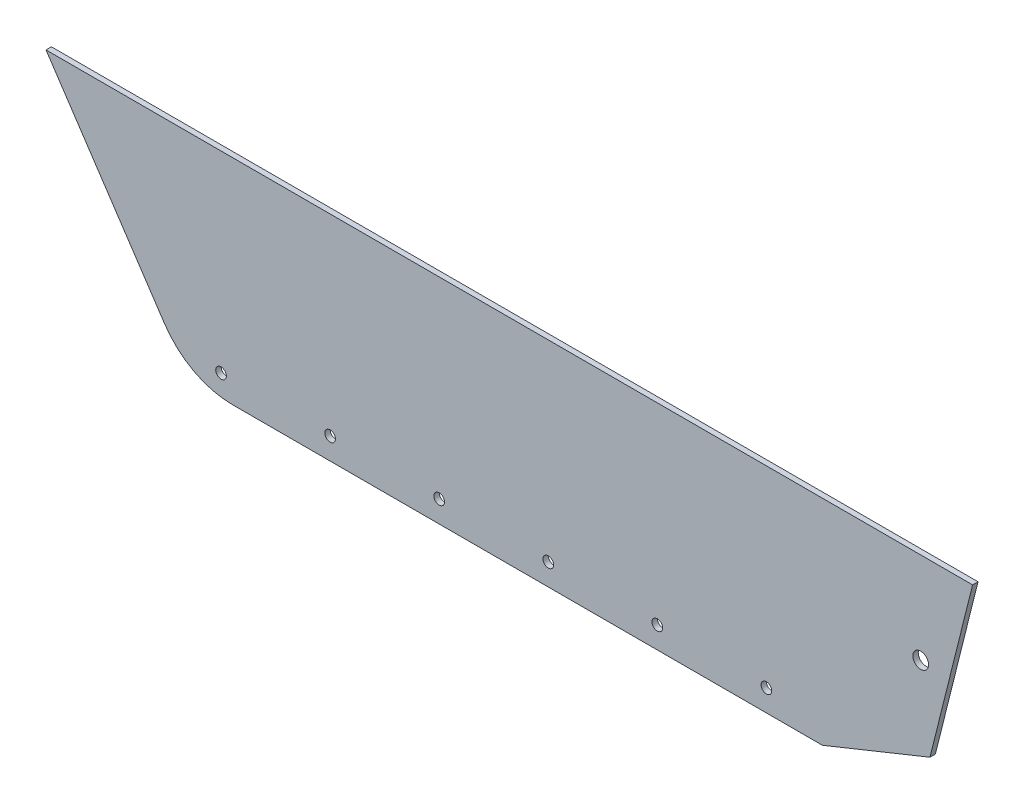
SolidWorks part; units mm, degrees
material "5052-H34"
ref_plane "Front Plane" through (0, 0, 0) normal (0, 0, 1) x (1, 0, 0)
ref_plane "Top Plane" through (0, 0, 0) normal (0, 1, 0) x (1, 0, 0)
ref_plane "Right Plane" through (0, 0, 0) normal (1, 0, 0) x (0, 0, -1)
sketch "Sketch1" plane through (0, 0, 0) normal (0, 0, 1) x (1, 0, 0)
  line L6 (-98.8794, 3.851) -> (-31.8794, -96.649)
  line L7 (428.1206, 28.9396) -> (403.1206, -71.149)
  line L9 (403.1206, -71.149) -> (366, -96.649)
  line L10 (-31.8794, -96.649) -> (366, -96.649)
  line L12 (-98.8794, 3.851) -> (-115.6052, 28.9396)
  line L13 (-115.6052, 28.9396) -> (428.1206, 28.9396)
  circle A0 centre (-12.8794, -83.899) radius 3.125
  circle A1 centre (51.1206, -83.899) radius 3.125
  circle A2 centre (115.1206, -83.899) radius 3.125
  circle A3 centre (179.1206, -83.899) radius 3.125
  circle A4 centre (243.1206, -83.899) radius 3.125
  circle A5 centre (307.1206, -83.899) radius 3.125
  point P0 (-48.8794, -71.149)
  point P2 (-31.8794, -96.649)
  point P8 (48, -83.899)
  point P9 (403.1206, -71.149)
  dimension "D2" = 64
  dimension "D4" = 64
  dimension "D15" = 6.25
  dimension "D1" = 25.5
  dimension "D3" = 75
  dimension "D5" = 25
  dimension "D6" = 96
  dimension "D7" = 527
  dimension "D8" = 180
  dimension "D9" = 64
  dimension "D10" = 64
  dimension "D11" = 64
  dimension "D12" = 123.69
  dimension "D13" = 12.75
  dimension "D14" = 543.7258
  dimension "D16" = 366
extrude "Boss-Extrude1" add sketch "Sketch1" along normal blind 3.175 contours L12 L13 L7 L9 L10 L6
extrude "Cut-Extrude1" cut sketch "Sketch1<4>" along normal through all contours A0 | A1 | A2 | A3 | A4 | A5 region at (-12.8794, -83.899, 0)
sketch "Sketch1<4>" plane through (0, 0, 0) normal (0, 0, 1) x (1, 0, 0) same geometry as "Sketch1"
sketch "Sketch2" plane through (0, 0, 0) normal (0, 0, -1) x (-1, 0, 0)
  circle A0 centre (-275.1206, -83.899) radius 6.5
  circle A2 centre (-233.5603, -132.5687) radius 6.5
  circle A3 centre (-192, -83.899) radius 6.5
  circle A4 centre (-128, -83.899) radius 6.5
  circle A5 centre (-64, -83.899) radius 6.5
  circle A6 centre (0, -83.899) radius 6.5
  dimension "D2" = 0
  dimension "D3" = 64
  dimension "D4" = 64
  dimension "D5" = 64
  dimension "D6" = 64
  dimension "D7" = 64
  dimension "D1" = 32
sketch "Sketch5" plane through (0, 0, 0) normal (0, 0, -1) x (-1, 0, 0)
  line L0 (48.8794, -71.149) -> (-14.2353, -96.649)
  line L1 (31.8794, -96.649) -> (-366, -96.649) construction
  line L2 (-14.2353, -96.649) -> (31.8794, -96.649)
  line L3 (31.8794, -96.649) -> (48.8794, -71.149)
  line L6 (-366, -96.649) -> (-403.1206, -71.149)
  line L7 (-403.1206, -71.149) -> (-352, -71.149)
  line L9 (-352, -71.149) -> (-326.5, -96.649)
  line L11 (-366, -96.649) -> (-326.5, -96.649)
  dimension "D1" = 22
  dimension "D2" = 45
extrude "Cut-Extrude2" [suppressed] cut sketch "Sketch5" against normal up to next
sketch "Sketch6" plane through (0, 0, 3.175) normal (0, 0, 1) x (1, 0, 0)
  line L0 (-48.8794, -71.149) -> (14.2353, -96.649)
  line L1 (-31.8794, -96.649) -> (366, -96.649) construction
  line L2 (14.2353, -96.649) -> (-31.8794, -96.649)
  line L3 (-31.8794, -96.649) -> (-48.8794, -71.149)
  dimension "D1" = 158
fillet "Fillet1" radius 48 1 edges at (-31.8794, -96.649, 1.5875)
sketch "Sketch7" plane through (0, 0, 3.175) normal (0, 0, 1) x (1, 0, 0)
  line L0 (403.1206, -71.149) -> (340.0059, -96.649)
  line L1 (-31.8794, -96.649) -> (366, -96.649) construction
  line L2 (340.0059, -96.649) -> (366, -96.649)
  line L3 (366, -96.649) -> (403.1206, -71.149)
  dimension "D1" = 22
extrude "Cut-Extrude3" cut sketch "Sketch7" against normal blind 10
sketch "Sketch9" plane through (0, 0, 0) normal (0, 0, -1) x (-1, 0, 0)
  line L0 (-403.1206, -71.149) -> (48.8794, -71.149)
  line L1 (48.8794, -71.149) -> (48.8794, -114.9143)
  line L2 (48.8794, -114.9143) -> (-403.1206, -114.9143)
  line L3 (-403.1206, -114.9143) -> (-403.1206, -71.149)
extrude "Cut-Extrude4" [suppressed] cut sketch "Sketch9" against normal blind 10
sketch "Sketch12" plane through (0, 0, 3.175) normal (0, 0, 1) x (1, 0, 0)
  circle A0 centre (397.6778, -24.6104) radius 4.625
  dimension "D1" = 9.25
extrude "Cut-Extrude5" cut sketch "Sketch12" against normal up to next
